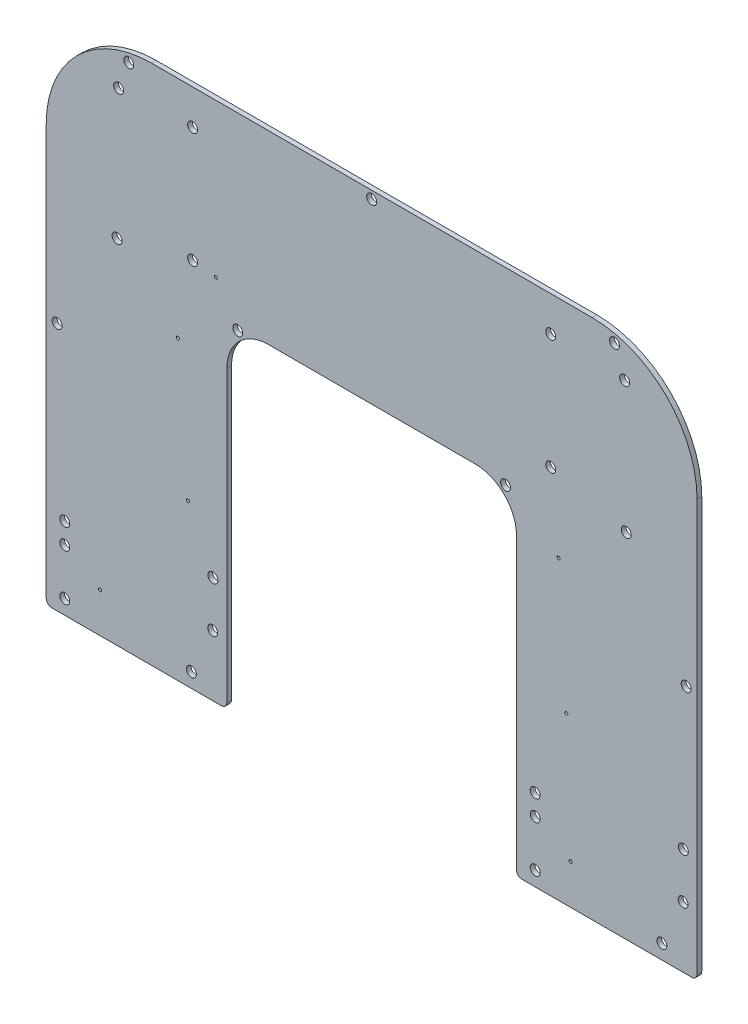
SolidWorks part; units mm, degrees
ref_plane "Front Plane" through (0, 0, 0) normal (0, 0, 1) x (1, 0, 0)
ref_plane "Top Plane" through (0, 0, 0) normal (0, 1, 0) x (1, 0, 0)
ref_plane "Right Plane" through (0, 0, 0) normal (1, 0, 0) x (0, 0, -1)
ref_axis "Axis1" through (0, 0, -88.99) along (0, 0, 1)
ref_axis "Axis2" through (0, -55, 0) along (0, 1, 0)
ref_axis "Axis3" through (-88.99, 0, 0) along (1, 0, 0)
sketch "Sketch1" plane through (0, 0, 0) normal (0, 0, 1) x (1, 0, 0)
  line L0 (0, 0) -> (0, 60)
  line L1 (0, 60) -> (-70.75, 60)
  line L2 (-104.75, 26) -> (-104.75, -106)
  line L3 (-102.75, -108) -> (-48.25, -108)
  line L4 (-46.25, -106) -> (-46.25, -13)
  line L5 (-33.25, 0) -> (0, 0)
  line L6 (0, 0) -> (0, -108) construction
  arc A0 (-70.75, 60) -> (-104.75, 26) centre (-70.75, 26) ccw
  arc A1 (-48.25, -108) -> (-46.25, -106) centre (-48.25, -106) ccw
  arc A2 (-104.75, -106) -> (-102.75, -108) centre (-102.75, -106) ccw
  arc A3 (-46.25, -13) -> (-33.25, 0) centre (-33.25, -13) cw
  point P12 (-46.25, -108)
  dimension "D4" = 34
  dimension "D6" = 2
  dimension "D7" = 13
  dimension "D1" = 92.5
  dimension "D2" = 209.5
  dimension "D3" = 60
  dimension "D5" = 168
extrude "Boss-Extrude1" add sketch "Sketch1" along normal blind 1.5
mirror "Mirror1" about plane through (0, 0, 0) normal (1, 0, 0) of bodies 101 103
hole_wizard "M3 Clearance Hole1" positions "Sketch4" profile "Sketch3" hole size "M3" standard "ANSI Metric" end condition through all
sketch "Sketch4" plane through (0, 0, 0) normal (0, 0, -1) x (-1, 0, 0)
  line L0 (0, 0) -> (0, 60) construction
  line L1 (-70.75, 60) -> (70.75, 60) construction
  circle A0 centre (51.0519, -88.1946) radius 1.524
  circle A1 centre (98.5499, -88.1946) radius 1.524
  circle A2 centre (-100.0104, -88.1946) radius 1.524
  circle A3 centre (-52.5124, -88.1946) radius 1.524
  point P0 (0, 57.25)
  point P2 (78, 56.25)
  point P4 (81.25, 47.5)
  point P6 (81.75, 5.5)
  point P8 (101, -27.75)
  point P10 (43, -0.75)
  point P12 (50.9757, -73.488)
  point P14 (57.8845, -103.079)
  point P16 (98.5499, -81.5652)
  point P18 (98.5499, -103.079)
  point P49 (-100.0866, -73.488)
  point P50 (-93.1778, -103.079)
  point P51 (-52.5124, -81.5652)
  point P52 (-52.5124, -103.079)
  point P63 (-43, -0.75)
  point P64 (-101, -27.75)
  point P65 (-81.75, 5.5)
  point P66 (-81.25, 47.5)
  point P67 (-78, 56.25)
  dimension "D22" = 3.048
  dimension "D31" = 3.048
  dimension "D1" = 0.5
  dimension "D2" = 42
  dimension "D3" = 2.75
  dimension "D4" = 78
  dimension "D5" = 1
  dimension "D6" = 81.25
  dimension "D7" = 51.75
  dimension "D8" = 58
  dimension "D9" = 43
  dimension "D10" = 85
  dimension "D11" = 101
  dimension "D12" = 6.9088
  dimension "D13" = 29.591
  dimension "D14" = 8.0772
  dimension "D15" = 47.5742
  dimension "D16" = 21.5138
  dimension "D17" = 50.9757
  dimension "D18" = 73.488
  dimension "D19" = 14.7066
  dimension "D20" = 0.0762
  dimension "D21" = 47.498
  dimension "D23" = 6.9088
  dimension "D24" = 29.591
  dimension "D25" = 8.0772
  dimension "D26" = 47.5742
  dimension "D27" = 21.5138
  dimension "D28" = 14.7066
  dimension "D29" = 0.0762
  dimension "D30" = 47.498
  dimension "D32" = 100.0866
sketch "Sketch3" plane through (0, 57.25, 0) normal (1, 0, 0) x (0, 1, 0)
  line L0 (0, 0) -> (0, 1.5)
  line L1 (0, 1.5) -> (1.6, 1.5)
  line L2 (1.6, 1.5) -> (1.6, 0)
  line L5 (1.6, 0) -> (0, 0)
  line L11 (0, -6.35) -> (0, 107.95) construction
  dimension "Thru Hole Dia." = 3.2
  dimension "Thru Hole Depth" = 1.5
hole_wizard "1/8 (0.125) Diameter Hole1" positions "Sketch6" profile "Sketch5" hole size "1/8" standard "ANSI Inch" end condition through all
sketch "Sketch6" plane through (0, 0, 0) normal (0, 0, -1) x (-1, 0, 0)
  point P0 (-100.0104, -88.1946)
  point P3 (-52.5124, -88.1946)
  point P6 (51.0519, -88.1946)
  point P9 (98.5499, -88.1946)
sketch "Sketch5" plane through (100.0104, -88.1946, 0) normal (1, 0, 0) x (0, 1, 0)
  line L0 (0, 0) -> (0, 1.5)
  line L1 (0, 1.5) -> (1.5875, 1.5)
  line L2 (1.5875, 1.5) -> (1.5875, 0)
  line L5 (1.5875, 0) -> (0, 0)
  line L11 (0, -6.35) -> (0, 107.95) construction
  dimension "Thru Hole Dia." = 3.175
  dimension "Thru Hole Depth" = 1.5
hole_wizard "M3 Clearance Hole2" positions "Sketch8" profile "Sketch7" hole size "M3" standard "ANSI Metric" end condition through all
sketch "Sketch8" plane through (0, 0, 0) normal (0, 0, -1) x (-1, 0, 0)
  line L0 (0, 48.5) -> (0, 30) construction
  line L1 (0, 30) -> (-57.5, 30) construction
  line L2 (33.25, 0) -> (-33.25, 0) construction
  line L3 (-70.75, 60) -> (70.75, 60) construction
  point P0 (-57.5, 48.5)
  point P12 (-57.5, 11.5)
  point P14 (57.5, 48.5)
  point P15 (57.5, 11.5)
  dimension "D1" = 115
  dimension "D2" = 37
sketch "Sketch7" plane through (57.5, 48.5, 0) normal (1, 0, 0) x (0, 1, 0)
  line L0 (0, 0) -> (0, 1.5)
  line L1 (0, 1.5) -> (1.6, 1.5)
  line L2 (1.6, 1.5) -> (1.6, 0)
  line L5 (1.6, 0) -> (0, 0)
  line L11 (0, -6.35) -> (0, 107.95) construction
  dimension "Thru Hole Dia." = 3.2
  dimension "Thru Hole Depth" = 1.5
sketch "Sketch10" plane through (0, 0, 0) normal (0, 0, -1) x (-1, 0, 0)
  line L0 (-70.75, 60) -> (70.75, 60) construction
  line L1 (-104.75, 26) -> (-104.75, -106) construction
  line L2 (-102.75, -108) -> (-48.25, -108) construction
  line L3 (-46.25, -106) -> (-46.25, -13) construction
  line L4 (33.25, 0) -> (-33.25, 0) construction
  line L5 (46.25, -106) -> (46.25, -13) construction
  line L6 (102.75, -108) -> (48.25, -108) construction
  line L7 (104.75, 26) -> (104.75, -106) construction
  line L8 (-70.75, 60) -> (70.75, 60)
  line L9 (-104.75, 26) -> (-104.75, -106)
  line L10 (-102.75, -108) -> (-48.25, -108)
  line L11 (-46.25, -106) -> (-46.25, -13)
  line L12 (33.25, 0) -> (-33.25, 0)
  line L13 (46.25, -106) -> (46.25, -13)
  line L14 (102.75, -108) -> (48.25, -108)
  line L15 (104.75, 26) -> (104.75, -106)
  line L16 (-70.75, 59.75) -> (70.75, 59.75)
  line L17 (104.5, 26) -> (104.5, -106)
  line L18 (102.75, -107.75) -> (48.25, -107.75)
  line L19 (46.5, -106) -> (46.5, -13)
  line L20 (33.25, 0.25) -> (-33.25, 0.25)
  line L21 (-46.5, -106) -> (-46.5, -13)
  line L22 (-102.75, -107.75) -> (-48.25, -107.75)
  line L23 (-104.5, 26) -> (-104.5, -106)
  arc A0 (-70.75, 60) -> (-104.75, 26) centre (-70.75, 26) ccw construction
  arc A1 (-104.75, -106) -> (-102.75, -108) centre (-102.75, -106) ccw construction
  arc A2 (-48.25, -108) -> (-46.25, -106) centre (-48.25, -106) ccw construction
  arc A3 (-33.25, 0) -> (-46.25, -13) centre (-33.25, -13) ccw construction
  arc A4 (46.25, -13) -> (33.25, 0) centre (33.25, -13) ccw construction
  arc A5 (46.25, -106) -> (48.25, -108) centre (48.25, -106) ccw construction
  arc A6 (102.75, -108) -> (104.75, -106) centre (102.75, -106) ccw construction
  arc A7 (104.75, 26) -> (70.75, 60) centre (70.75, 26) ccw construction
  arc A8 (-70.75, 60) -> (-104.75, 26) centre (-70.75, 26) ccw
  arc A9 (-104.75, -106) -> (-102.75, -108) centre (-102.75, -106) ccw
  arc A10 (-48.25, -108) -> (-46.25, -106) centre (-48.25, -106) ccw
  arc A11 (-33.25, 0) -> (-46.25, -13) centre (-33.25, -13) ccw
  arc A12 (46.25, -13) -> (33.25, 0) centre (33.25, -13) ccw
  arc A13 (46.25, -106) -> (48.25, -108) centre (48.25, -106) ccw
  arc A14 (102.75, -108) -> (104.75, -106) centre (102.75, -106) ccw
  arc A15 (104.75, 26) -> (70.75, 60) centre (70.75, 26) ccw
  arc A16 (104.5, 26) -> (70.75, 59.75) centre (70.75, 26) ccw
  arc A17 (102.75, -107.75) -> (104.5, -106) centre (102.75, -106) ccw
  arc A18 (46.5, -106) -> (48.25, -107.75) centre (48.25, -106) ccw
  arc A19 (46.5, -13) -> (33.25, 0.25) centre (33.25, -13) ccw
  arc A20 (-33.25, 0.25) -> (-46.5, -13) centre (-33.25, -13) ccw
  arc A21 (-48.25, -107.75) -> (-46.5, -106) centre (-48.25, -106) ccw
  arc A22 (-104.5, -106) -> (-102.75, -107.75) centre (-102.75, -106) ccw
  arc A23 (-70.75, 59.75) -> (-104.5, 26) centre (-70.75, 26) ccw
  dimension "D1" = 0.25
extrude "Cut-Extrude1" cut sketch "Sketch10" against normal through all
sketch "Sketch11" plane through (0, 0, 0) normal (0, 0, -1) x (-1, 0, 0)
  circle A0 centre (-60, -12.5) radius 0.5
  arc A1 (-63.7059, -4.5942) -> (-56.2941, -4.5942) centre (-60, -12.5) ccw construction
  circle A2 centre (-62.5, -54.4437) radius 0.5
  arc A3 (-66.2059, -46.538) -> (-58.7941, -46.538) centre (-62.5, -54.4437) ccw construction
  circle A4 centre (59, -56.0874) radius 0.5
  arc A5 (55.6664, -49.7691) -> (62.3336, -49.7691) centre (59, -56.0874) ccw construction
  circle A6 centre (62.25, -12.5) radius 0.5
  arc A7 (56.7608, -2.835) -> (67.7392, -2.835) centre (62.25, -12.5) ccw construction
  circle A8 centre (-63.8789, -94.9764) radius 0.5
  circle A9 centre (-63.8789, -94.9764) radius 0.7877 construction
  circle A10 centre (87.1961, -94.9764) radius 0.5
  circle A11 centre (87.1961, -94.9764) radius 0.7877 construction
  circle A12 centre (50.02, 10.5) radius 0.5
  circle A13 centre (50.02, 10.5) radius 0.5 construction
  dimension "D1" = 1
extrude "Cut-Extrude2" cut sketch "Sketch11" against normal through all
sketch "Sketch12" plane through (0, 0, 0) normal (0, 0, -1) x (-1, 0, 0)
  line L0 (-85.1179, 49.6748) -> (-80.9432, 52.5979) construction
  line L1 (-87.25, 41) -> (-87.25, 45.579) construction
  line L2 (-87.25, 2.5) -> (-87.25, 17) construction
  line L3 (-77.75, 1) -> (-85.75, 1) construction
  line L4 (-76.25, 15.1061) -> (-76.25, 2.5) construction
  line L5 (-76.25, 41) -> (-87.25, 41) construction
  line L6 (-76.25, 43.7463) -> (-76.25, 41) construction
  line L7 (-78.8541, 52.2296) -> (-75.7137, 47.7446) construction
  line L8 (-76.25, 15.1061) -> (-83.75, 15.1061) construction
  line L9 (-85.1179, 49.6748) -> (-80.9432, 52.5979) construction
  line L10 (-87.25, 41) -> (-87.25, 45.579) construction
  line L11 (-87.25, 2.5) -> (-87.25, 17) construction
  line L12 (-77.75, 1) -> (-85.75, 1) construction
  line L13 (-76.25, 15.1061) -> (-76.25, 2.5) construction
  line L14 (-76.25, 41) -> (-87.25, 41) construction
  line L15 (-76.25, 43.7463) -> (-76.25, 41) construction
  line L16 (-78.8541, 52.2296) -> (-75.7137, 47.7446) construction
  line L17 (-76.25, 15.1061) -> (-83.75, 15.1061) construction
  line L18 (-83.75, 17) -> (-83.75, 15.1061) construction
  line L19 (-83.75, 17) -> (-83.75, 15.1061) construction
  line L20 (-83.75, 17) -> (-87.25, 17) construction
  line L21 (-83.75, 17) -> (-87.25, 17) construction
  line L22 (76.25, 15.1061) -> (83.75, 15.1061) construction
  line L23 (76.25, 15.1061) -> (76.25, 2.5) construction
  line L24 (76.25, 43.7463) -> (76.25, 41) construction
  line L25 (78.8541, 52.2296) -> (75.7137, 47.7446) construction
  line L26 (85.1179, 49.6748) -> (80.9432, 52.5979) construction
  line L27 (87.25, 41) -> (87.25, 45.579) construction
  line L28 (87.25, 2.5) -> (87.25, 17) construction
  line L29 (83.75, 17) -> (87.25, 17) construction
  line L30 (76.25, 41) -> (87.25, 41) construction
  line L31 (77.75, 1) -> (85.75, 1) construction
  line L32 (83.75, 17) -> (83.75, 15.1061) construction
  line L33 (76.25, 15.1061) -> (83.75, 15.1061) construction
  line L34 (76.25, 15.1061) -> (76.25, 2.5) construction
  line L35 (76.25, 43.7463) -> (76.25, 41) construction
  line L36 (78.8541, 52.2296) -> (75.7137, 47.7446) construction
  line L37 (85.1179, 49.6748) -> (80.9432, 52.5979) construction
  line L38 (87.25, 41) -> (87.25, 45.579) construction
  line L39 (87.25, 2.5) -> (87.25, 17) construction
  line L40 (83.75, 17) -> (87.25, 17) construction
  line L41 (76.25, 41) -> (87.25, 41) construction
  line L42 (77.75, 1) -> (85.75, 1) construction
  line L43 (83.75, 17) -> (83.75, 15.1061) construction
  line L44 (-75.75, 40.5) -> (-87.75, 40.5)
  line L45 (-87.75, 40.5) -> (-87.75, 45.579)
  line L46 (-85.4047, 50.0844) -> (-81.23, 53.0075)
  line L47 (-78.4445, 52.5163) -> (-75.3041, 48.0314)
  line L48 (-75.75, 43.7463) -> (-75.75, 40.5)
  line L49 (-83.25, 17.5) -> (-87.75, 17.5)
  line L50 (-87.75, 2.5) -> (-87.75, 17.5)
  line L51 (-77.75, 0.5) -> (-85.75, 0.5)
  line L52 (-75.75, 15.6061) -> (-75.75, 2.5)
  line L53 (-75.75, 15.6061) -> (-83.25, 15.6061)
  line L54 (-83.25, 17.5) -> (-83.25, 15.6061)
  line L55 (75.75, 15.6061) -> (83.25, 15.6061)
  line L56 (83.25, 17.5) -> (83.25, 15.6061)
  line L57 (83.25, 17.5) -> (87.75, 17.5)
  line L58 (87.75, 2.5) -> (87.75, 17.5)
  line L59 (77.75, 0.5) -> (85.75, 0.5)
  line L60 (75.75, 15.6061) -> (75.75, 2.5)
  line L61 (75.75, 40.5) -> (87.75, 40.5)
  line L62 (87.75, 40.5) -> (87.75, 45.579)
  line L63 (85.4047, 50.0844) -> (81.23, 53.0075)
  line L64 (78.4445, 52.5163) -> (75.3041, 48.0314)
  line L65 (75.75, 43.7463) -> (75.75, 40.5)
  arc A0 (-85.1179, 49.6748) -> (-87.25, 45.579) centre (-82.25, 45.579) ccw construction
  arc A1 (-87.25, 2.5) -> (-85.75, 1) centre (-85.75, 2.5) ccw construction
  arc A2 (-77.75, 1) -> (-76.25, 2.5) centre (-77.75, 2.5) ccw construction
  arc A3 (-75.6288, 46.1601) -> (-76.25, 43.7463) centre (-71.25, 43.7463) ccw construction
  arc A4 (-75.6288, 46.1601) -> (-75.7137, 47.7446) centre (-76.9424, 46.8842) ccw construction
  arc A5 (-85.1179, 49.6748) -> (-87.25, 45.579) centre (-82.25, 45.579) ccw construction
  arc A6 (-87.25, 2.5) -> (-85.75, 1) centre (-85.75, 2.5) ccw construction
  arc A7 (-77.75, 1) -> (-76.25, 2.5) centre (-77.75, 2.5) ccw construction
  arc A8 (-75.6288, 46.1601) -> (-76.25, 43.7463) centre (-71.25, 43.7463) ccw construction
  arc A9 (-75.6288, 46.1601) -> (-75.7137, 47.7446) centre (-76.9424, 46.8842) ccw construction
  arc A10 (-78.8541, 52.2296) -> (-80.9432, 52.5979) centre (-80.0828, 51.3692) ccw construction
  arc A11 (-78.8541, 52.2296) -> (-80.9432, 52.5979) centre (-80.0828, 51.3692) ccw construction
  arc A12 (76.25, 2.5) -> (77.75, 1) centre (77.75, 2.5) ccw construction
  arc A13 (76.25, 43.7463) -> (75.6288, 46.1601) centre (71.25, 43.7463) ccw construction
  arc A14 (75.7137, 47.7446) -> (75.6288, 46.1601) centre (76.9424, 46.8842) ccw construction
  arc A15 (80.9432, 52.5979) -> (78.8541, 52.2296) centre (80.0828, 51.3692) ccw construction
  arc A16 (87.25, 45.579) -> (85.1179, 49.6748) centre (82.25, 45.579) ccw construction
  arc A17 (85.75, 1) -> (87.25, 2.5) centre (85.75, 2.5) ccw construction
  arc A18 (76.25, 2.5) -> (77.75, 1) centre (77.75, 2.5) ccw construction
  arc A19 (76.25, 43.7463) -> (75.6288, 46.1601) centre (71.25, 43.7463) ccw construction
  arc A20 (75.7137, 47.7446) -> (75.6288, 46.1601) centre (76.9424, 46.8842) ccw construction
  arc A21 (80.9432, 52.5979) -> (78.8541, 52.2296) centre (80.0828, 51.3692) ccw construction
  arc A22 (87.25, 45.579) -> (85.1179, 49.6748) centre (82.25, 45.579) ccw construction
  arc A23 (85.75, 1) -> (87.25, 2.5) centre (85.75, 2.5) ccw construction
  arc A24 (-85.4047, 50.0844) -> (-87.75, 45.579) centre (-82.25, 45.579) ccw
  arc A25 (-78.4445, 52.5163) -> (-81.23, 53.0075) centre (-80.0828, 51.3692) ccw
  arc A26 (-75.1909, 45.9187) -> (-75.3041, 48.0314) centre (-76.9424, 46.8842) ccw
  arc A27 (-75.1909, 45.9187) -> (-75.75, 43.7463) centre (-71.25, 43.7463) ccw
  arc A28 (-87.75, 2.5) -> (-85.75, 0.5) centre (-85.75, 2.5) ccw
  arc A29 (-77.75, 0.5) -> (-75.75, 2.5) centre (-77.75, 2.5) ccw
  arc A30 (85.75, 0.5) -> (87.75, 2.5) centre (85.75, 2.5) ccw
  arc A31 (75.75, 2.5) -> (77.75, 0.5) centre (77.75, 2.5) ccw
  arc A32 (87.75, 45.579) -> (85.4047, 50.0844) centre (82.25, 45.579) ccw
  arc A33 (81.23, 53.0075) -> (78.4445, 52.5163) centre (80.0828, 51.3692) ccw
  arc A34 (75.3041, 48.0314) -> (75.1909, 45.9187) centre (76.9424, 46.8842) ccw
  arc A35 (75.75, 43.7463) -> (75.1909, 45.9187) centre (71.25, 43.7463) ccw
  dimension "D1" = 0.5
extrude "Boss-Extrude2" [suppressed] add sketch "Sketch12" along normal blind 2.5 separate body
sketch "Sketch13" [suppressed] plane through (0, 0, 0) normal (0, 0, 1) x (1, 0, 0)
  circle A0 centre (81.25, 47.75) radius 1.6 construction
  circle A1 centre (81.75, 5.75) radius 1.6 construction
  circle A2 centre (81.25, 47.75) radius 1.6
  circle A3 centre (81.75, 5.75) radius 1.6
extrude "Cut-Extrude4" [suppressed] cut sketch "Sketch13" against normal through all
equation "\"D31@Sketch4\"=\"D22@Sketch4\""
equation "\"D26@Sketch4\"=\"D15@Sketch4\""
equation "\"D23@Sketch4\"=\"D12@Sketch4\""
equation "\"D25@Sketch4\"=\"D14@Sketch4\""
equation "\"D24@Sketch4\"=\"D13@Sketch4\""
equation "\"D27@Sketch4\"=\"D16@Sketch4\""
equation "\"D28@Sketch4\"=\"D19@Sketch4\""
equation "\"D29@Sketch4\"=\"D20@Sketch4\""
equation "\"D30@Sketch4\"=\"D21@Sketch4\""
